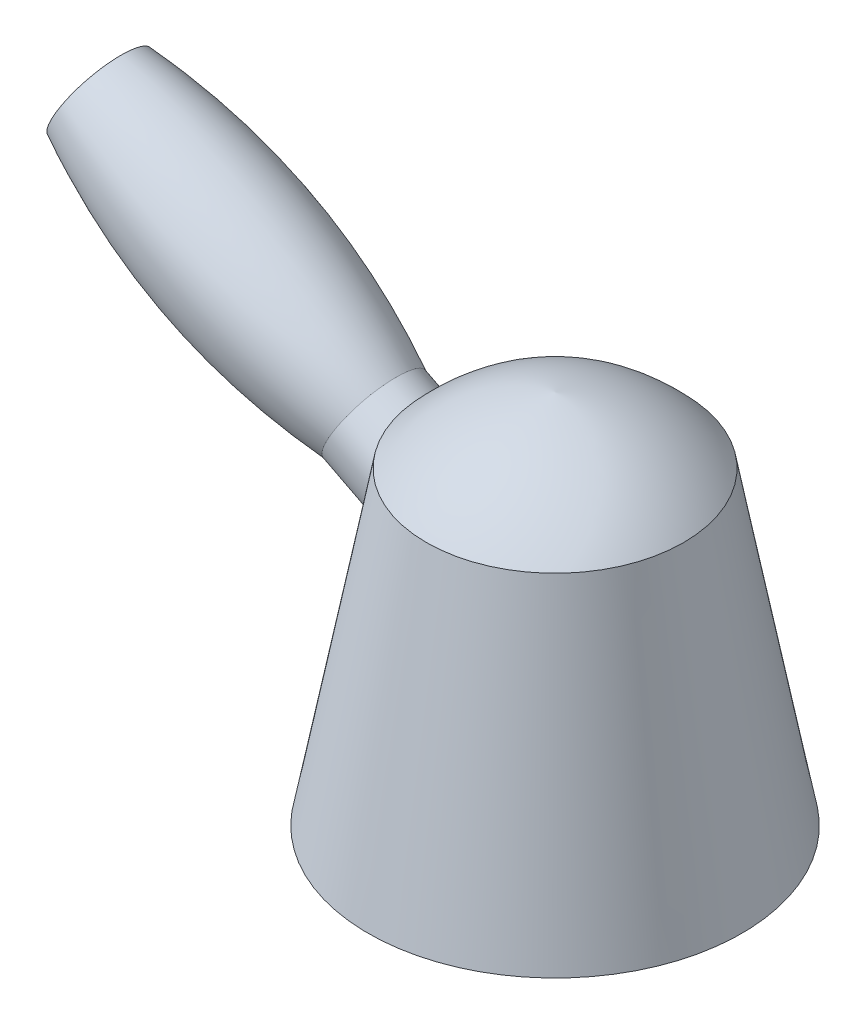
SolidWorks part; units mm, degrees
material "ABS"
ref_plane "Front Plane" through (0, 0, 0) normal (0, 0, 1) x (1, 0, 0)
ref_plane "Top Plane" through (0, 0, 0) normal (0, 1, 0) x (1, 0, 0)
ref_plane "Right Plane" through (0, 0, 0) normal (1, 0, 0) x (0, 0, -1)
sketch "Sketch1" plane through (0, 0, 0) normal (0, 0, 1) x (1, 0, 0)
  line L0 (-31, 0) -> (-21.3466, 51.3227)
  line L2 (-13, 0) -> (-13, 38)
  line L3 (-13, 0) -> (-31, 0)
  line L5 (-13, 38) -> (0, 38)
  line L6 (0, 62.2231) -> (0, 0)
  spline S0 degree 2 poles (-21.3466, 51.3227) (-12.7328, 60.5935) (0, 62.2231) knots 0 0 0 1 1 1
revolve "Revolve2" add sketch "Sketch1" angle 360 about L6 region at (-15.7749, 31.3448, 0)
ref_point "Point1"
ref_axis "Axis1" through (0, 0, 0) along (0, 1, 0)
sketch "Sketch3" plane through (0, 0, 0) normal (0, 0, 1) x (1, 0, 0)
  line L0 (-19.1245, 38.5527) -> (-75.6217, 67.6245)
  line L1 (-75.6217, 67.6245) -> (-72.0085, 74.6462)
  line L2 (-26.393, 51.1738) -> (-15.5114, 45.5744)
  line L3 (-15.5114, 45.5744) -> (-19.1245, 38.5527)
  spline S0 degree 2 poles (-72.0085, 74.6462) (-46.3258, 68.7843) (-26.393, 51.1738) knots 0 0 0 1 1 1
revolve "Revolve3" add sketch "Sketch3" angle 360 about L0
